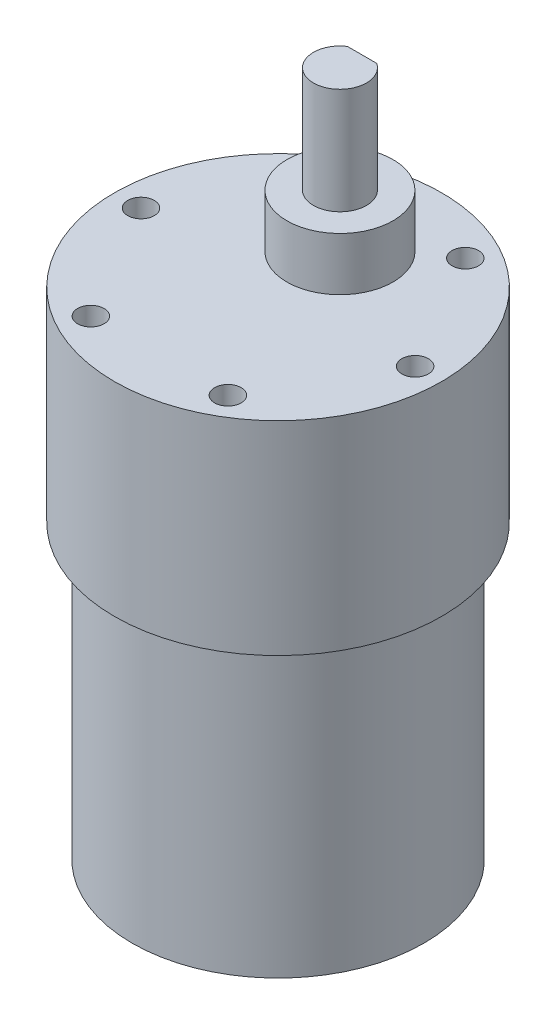
SolidWorks part; units mm, degrees
ref_plane "前视基准面" through (0, 0, 0) normal (0, 0, 1) x (1, 0, 0)
ref_plane "上视基准面" through (0, 0, 0) normal (0, 1, 0) x (1, 0, 0)
ref_plane "右视基准面" through (0, 0, 0) normal (1, 0, 0) x (0, 0, -1)
sketch "草图1" plane through (0, 0, 0) normal (0, 1, 0) x (1, 0, 0)
  circle A0 centre (0, 0) radius 16.5
  circle A1 centre (0, 0) radius 18.5
  dimension "D1" = 33
  dimension "D2" = 37
extrude "凸台-拉伸1" add sketch "草图1" against normal blind 33 contours A0
extrude "凸台-拉伸2" add sketch "草图1<3>" along normal blind 23 contours A1
sketch "草图1<3>" plane through (0, 0, 0) normal (0, 1, 0) x (1, 0, 0) same geometry as "草图1"
sketch "草图3" plane through (0, 23, 0) normal (0, 1, 0) x (1, 0, 0)
  line L0 (0, 18.5) -> (0, -18.5) construction
  line L2 (7.75, -13.4234) -> (15.5, 0) construction
  line L3 (15.5, 0) -> (7.75, 13.4234) construction
  line L4 (7.75, 13.4234) -> (-7.75, 13.4234) construction
  line L5 (-7.75, 13.4234) -> (-15.5, 0) construction
  line L6 (-15.5, 0) -> (-7.75, -13.4234) construction
  line L7 (-7.75, -13.4234) -> (7.75, -13.4234) construction
  circle A0 centre (0, 0) radius 18.5 construction
  circle A1 centre (0, 7) radius 6
  circle A2 centre (0, 7) radius 3
  circle A3 centre (0, 0) radius 15.5 construction
  circle A4 centre (-7.75, 13.4234) radius 1.5
  circle A5 centre (7.75, 13.4234) radius 1.5
  circle A6 centre (15.5, 0) radius 1.5
  circle A7 centre (7.75, -13.4234) radius 1.5
  circle A8 centre (-7.75, -13.4234) radius 1.5
  circle A9 centre (-15.5, 0) radius 1.5
  point P29 (0, 0)
  dimension "D1" = 7
  dimension "D2" = 12
  dimension "D3" = 6
  dimension "D4" = 6
  dimension "D5" = 31
  dimension "D6" = 30
extrude "切除-拉伸1" cut sketch "草图3" against normal blind 2.5 contours A4 | A9 | A8 | A7 | A6 | A5
extrude "凸台-拉伸3" add sketch "草图3<3>" along normal blind 18 contours A2
sketch "草图3<3>" plane through (0, 23, 0) normal (0, 1, 0) x (1, 0, 0) same geometry as "草图3"
extrude "凸台-拉伸4" add sketch "草图3<4>" along normal blind 6 contours A1
sketch "草图3<4>" plane through (0, 23, 0) normal (0, 1, 0) x (1, 0, 0) same geometry as "草图3"
sketch "草图4" plane through (0, 41, 0) normal (0, 1, 0) x (1, 0, 0)
  line L0 (-1.6583, 9.5) -> (1.6583, 9.5)
  arc A0 (1.6583, 9.5) -> (-1.6583, 9.5) centre (0, 7) ccw
  dimension "D1" = 2.5
extrude "切除-拉伸2" cut sketch "草图4" against normal blind 12
sketch "草图5" plane through (0, -33, 0) normal (0, -1, 0) x (1, 0, 0)
  circle A0 centre (0, 0) radius 5.7642
